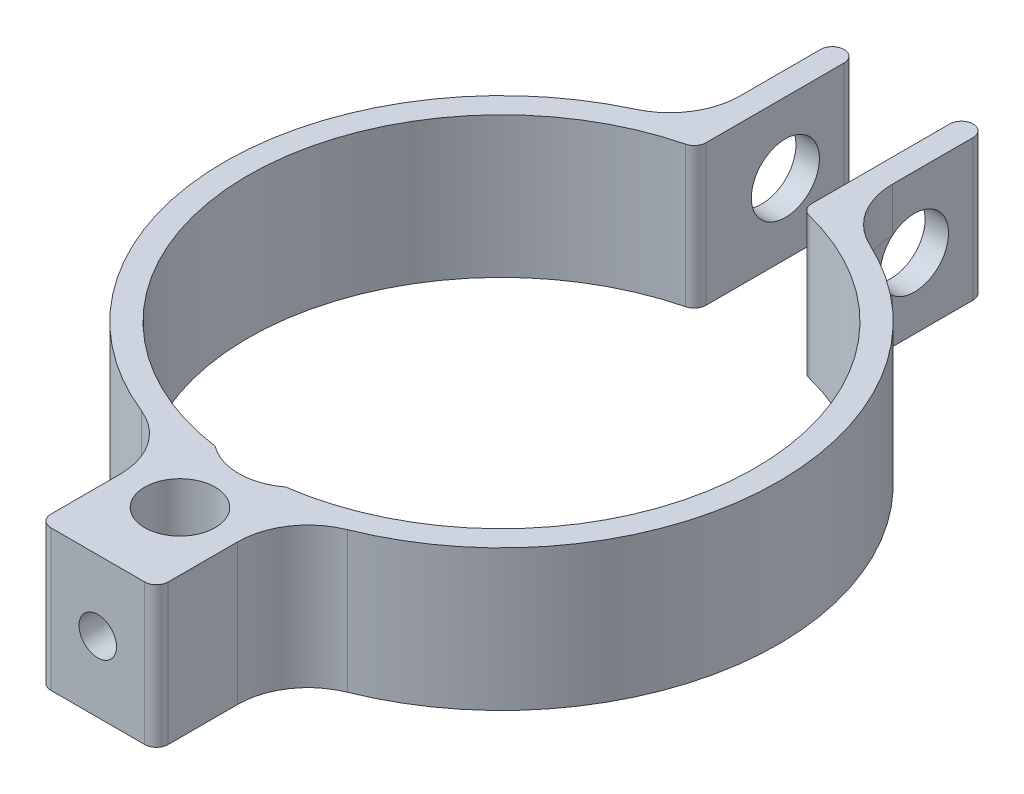
SolidWorks part; units mm, degrees
ref_plane "Plan de face" through (0, 0, 0) normal (0, 0, 1) x (1, 0, 0)
ref_plane "Plan de dessus" through (0, 0, 0) normal (0, 1, 0) x (1, 0, 0)
ref_plane "Plan de droite" through (0, 0, 0) normal (1, 0, 0) x (0, 0, -1)
sketch "Esquisse1" plane through (0, 0, 0) normal (0, 1, 0) x (1, 0, 0)
  line L0 (0, -3.3) -> (0, 3.3) construction
  line L2 (-3.25, 11.3436) -> (-3.25, 17.3436)
  line L3 (-3.25, 17.3436) -> (-2.25, 17.3436)
  line L4 (3.25, 11.3436) -> (3.25, 17.3436)
  line L5 (-2.25, 10.563) -> (-2.25, 17.3436)
  line L6 (2.25, 10.563) -> (2.25, 17.3436)
  line L7 (2.25, 17.3436) -> (3.25, 17.3436)
  line L8 (0, -11.2) -> (0, -16.2) construction
  line L10 (-2.5, -13.7) -> (-2.5, -16.2)
  line L11 (-2.5, -16.2) -> (2.5, -16.2) construction
  line L12 (2.5, -13.7) -> (2.5, -16.2)
  line L13 (-2.5, -16.2) -> (-2.5, -17.2)
  line L14 (-2.5, -17.2) -> (2.5, -17.2)
  line L15 (2.5, -17.2) -> (2.5, -16.2)
  arc A0 (-2.25, 10.563) -> (-1.5, -10.6953) centre (0, 0) ccw
  arc A1 (-3.25, 11.3436) -> (-1.5049, -11.7036) centre (0, 0) ccw
  arc A2 (1.5049, -11.7036) -> (2.5, -13.7) centre (0, -13.7) cw
  circle A3 centre (0, -13.7) radius 1.5
  arc A4 (1.5049, -11.7036) -> (3.25, 11.3436) centre (0, 0) ccw
  arc A5 (-2.5, -13.7) -> (-1.5049, -11.7036) centre (0, -13.7) cw
  arc A6 (-1.5, -10.6953) -> (1.5, -10.6953) centre (0, -8.7185) ccw
  arc A7 (1.5, -10.6953) -> (2.25, 10.563) centre (0, 0) ccw
  arc A8 (-1.5, -10.6953) -> (1.5, -10.6953) centre (0, 0) ccw construction
  point P24 (0, -13.7)
  point P29 (0, -10.8)
  point P30 (0, -15.2)
  dimension "D1" = 21.6
  dimension "D2" = 1
  dimension "D6" = 1
  dimension "D8" = 3
  dimension "D9" = 0.4
  dimension "D10" = 3
  dimension "D3" = 1
  dimension "D4" = 4.5
  dimension "D5" = 6
  dimension "D7" = 5
  dimension "D11" = 2
extrude "Boss.-Extru.1" add sketch "Esquisse1" along normal mid plane 6
sketch "Esquisse3" plane through (-3.25, 0, 0) normal (-1, 0, 0) x (0, 0, 1)
  line L0 (12.98, 0) -> (-12.98, 0) construction
  line L1 (-17.3436, 0) -> (-11.3436, 0) construction
  line L2 (-17.3436, 3) -> (-17.3436, -3) construction
  line L3 (-11.3436, 3) -> (-11.3436, -3) construction
  circle A0 centre (-14.3436, 0) radius 1.45
  point P11 (-14.3436, 0)
  dimension "D1" = 2.9
hole_wizard "Trou pour taraudage pour trou taraudé M21" positions "Esquisse4" profile "Esquisse5" hole size "M2" standard "ISO" end condition up to next
sketch "Esquisse4" plane through (0, 0, 17.2) normal (0, 0, 1) x (1, 0, 0)
  line L0 (12.98, 0) -> (-12.98, 0) construction
  line L1 (0, -3.3) -> (0, 3.3) construction
  point P0 (0, 0)
sketch "Esquisse5" plane through (0, 0, 17.2) normal (1, 0, 0) x (0, -1, 0)
  line L0 (0, 0) -> (0, 2)
  line L1 (0, 2) -> (0.8, 2)
  line L2 (0.8, 2) -> (0.8, 0)
  line L5 (0.8, 0) -> (0, 0)
  line L11 (0, -6.35) -> (0, 107.95) construction
  dimension "Diamètre du perçage jusqu'au prochain" = 1.6
  dimension "Profondeur du perçage jusqu'au prochain" = 2
extrude "Enlèv. mat.-Extru.1" cut sketch "Esquisse3" against normal through all
fillet "Congé1" radius 3 4 edges at (-1.5049, 0, 11.7036) (1.5049, 0, 11.7036) (3.25, 0, -11.3436) (-3.25, 0, -11.3436)
fillet "Congé2" radius 0.5 8 edges at (3.25, 0, -17.3436) (2.25, 0, -17.3436) (-2.25, 0, -17.3436) (-3.25, 0, -17.3436) (-2.25, 0, -10.563) (2.25, 0, -10.563) (2.5, 0, 17.2) (-2.5, 0, 17.2)
